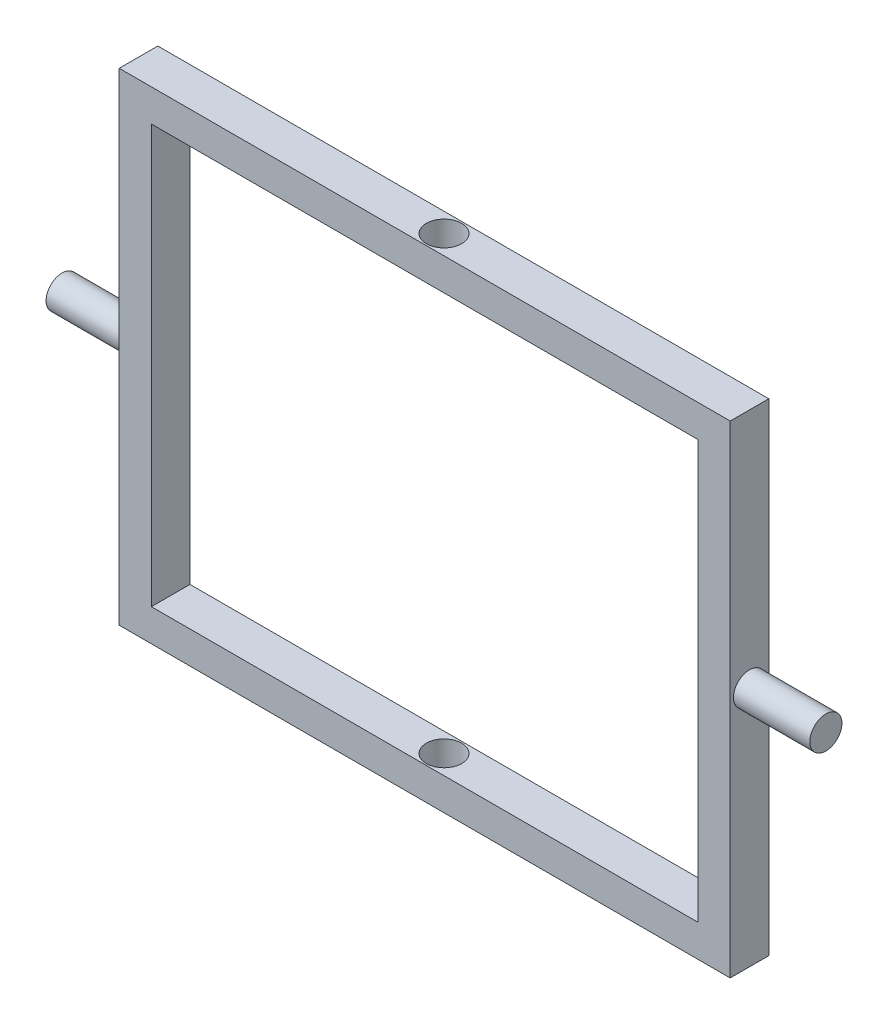
SolidWorks part; units mm, degrees
ref_plane "Front Plane" through (0, 0, 0) normal (0, 0, 1) x (1, 0, 0)
ref_plane "Top Plane" through (0, 0, 0) normal (0, 1, 0) x (1, 0, 0)
ref_plane "Right Plane" through (0, 0, 0) normal (1, 0, 0) x (0, 0, -1)
sketch "Sketch1" plane through (0, 0, 0) normal (0, 0, 1) x (1, 0, 0)
  line L1 (-425, 325) -> (425, 325)
  line L2 (-425, 325) -> (-425, -325)
  line L3 (-425, -325) -> (425, -325)
  line L4 (425, 325) -> (425, -325)
  line L5 (-425, 325) -> (425, -325) construction
  line L6 (-425, -325) -> (425, 325) construction
  line L7 (-475, 375) -> (475, 375)
  line L8 (-475, 375) -> (-475, -375)
  line L9 (-475, -375) -> (475, -375)
  line L10 (475, 375) -> (475, -375)
  line L11 (-475, 375) -> (475, -375) construction
  line L12 (-475, -375) -> (475, 375) construction
  point P0 (0, 0)
  point P6 (0, 0)
  dimension "D1" = 850
  dimension "D2" = 650
  dimension "D3" = 750
  dimension "D4" = 950
extrude "Boss-Extrude1" add sketch "Sketch1" along normal blind 30 and the other way blind 30
sketch "Sketch3" plane through (475, 0, 0) normal (1, 0, 0) x (0, 0, -1)
  circle A0 centre (0, 0) radius 25
  dimension "D1" = 50
extrude "Boss-Extrude2" add sketch "Sketch3" along normal blind 118.75
mirror "Mirror2" about plane through (0, 0, 0) normal (1, 0, 0) of "Boss-Extrude2"
sketch "Sketch4" plane through (0, 325, 0) normal (0, -1, 0) x (1, 0, 0)
  circle A0 centre (0, 0) radius 27.5
  dimension "D1" = 55
extrude "Cut-Extrude2" cut sketch "Sketch4" against normal blind 85
mirror "Mirror3" about plane through (0, 0, 0) normal (0, 1, 0) of "Cut-Extrude2"
